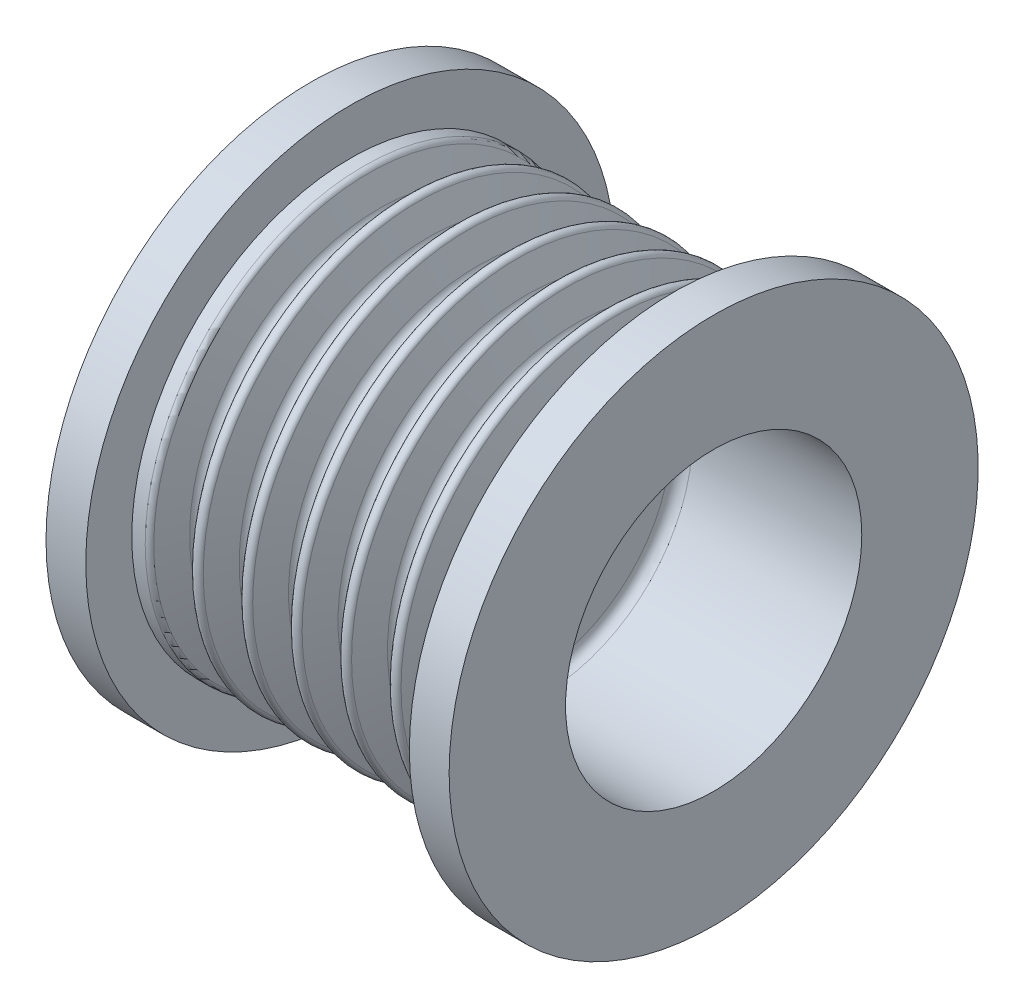
SolidWorks part; units mm, degrees
ref_plane "Front Plane" through (0, 0, 0) normal (0, 0, 1) x (1, 0, 0)
ref_plane "Top Plane" through (0, 0, 0) normal (0, 1, 0) x (1, 0, 0)
ref_plane "Right Plane" through (0, 0, 0) normal (1, 0, 0) x (0, 0, -1)
sketch "Sketch1" plane through (0, 0, 0) normal (0, 0, 1) x (1, 0, 0)
  line L4 (3, 12.5) -> (22.05, 12.5)
  line L5 (22.05, 12.5) -> (22.05, 4)
  line L10 (0, 0) -> (24, 0) construction
  line L12 (0, 4) -> (22.05, 4)
  line L13 (0, 4) -> (0, 8)
  line L14 (0, 8) -> (3, 8)
  line L15 (3, 8) -> (3, 12.5)
  dimension "D2" = 8
  dimension "D3" = 25
  dimension "D1" = 3
  dimension "D4" = 16
  dimension "D5" = 19.05
revolve "Revolve1" add sketch "Sketch1" angle 360 about L10
sketch "Sketch2" plane through (0, 0, 0) normal (0, 0, 1) x (1, 0, 0)
  line L0 (22.05, 0) -> (3, 0) construction
  line L1 (22.05, -12.5) -> (22.05, 12.5) construction
  line L3 (12.525, 0) -> (12.525, 12.5) construction
  line L4 (22.05, 12.5) -> (3, 12.5) construction
  line L5 (17.1986, 12.5) -> (19.5354, 12.5)
  line L6 (17.1986, 12.5) -> (17.1986, 10.3271)
  line L7 (19.5354, 12.5) -> (19.5354, 10.3271)
  line L8 (17.1986, 11.43) -> (19.5354, 11.43) construction
  line L9 (17.4373, 10.16) -> (17.8896, 8.9172)
  line L11 (18.8444, 8.9172) -> (19.2967, 10.16)
  line L12 (17.4373, 10.16) -> (19.2967, 10.16) construction
  line L13 (12.525, 12.5) -> (14.8618, 12.5) construction
  line L14 (14.8618, 12.5) -> (17.1986, 12.5) construction
  arc A0 (17.1986, 10.3271) -> (17.4373, 10.16) centre (17.1986, 10.0731) cw
  arc A1 (17.8896, 8.9172) -> (18.8444, 8.9172) centre (18.367, 9.0909) ccw
  arc A2 (19.5354, 10.3271) -> (19.2967, 10.16) centre (19.5354, 10.0731) ccw
  point P4 (0, 0)
  point P12 (0, 0)
  point P24 (9.525, -1.2265)
  point P25 (9.525, 0.8358)
  point P26 (0, 0)
  point P28 (9.525, 0)
  dimension "D3" = 0.254
  dimension "D6" = 0.508
  dimension "D1" = 2.3368
  dimension "D2" = 11.43
  dimension "D4" = 40
  dimension "D5" = 1.27
revolve "tooth groove" cut sketch "Sketch2" angle 360 about L0
pattern_linear "LPattern1" count 6 spacing 2.3368 along (-1, 0, 0) of "tooth groove"
sketch "Sketch3" plane through (0, 0, 0) normal (0, 0, 1) x (1, 0, 0)
  line L0 (22.05, 12.5) -> (19.5354, 12.5) construction
  line L2 (19.5354, 10.3271) -> (20.1704, 10.3271)
  line L4 (19.5354, 10.3271) -> (19.5354, 12.5)
  line L5 (19.5354, 12.5) -> (20.1704, 12.5)
  line L6 (20.1704, 10.3271) -> (20.1704, 12.5)
  line L7 (18.367, 8.5829) -> (18.367, 11.0958) construction
  line L8 (12.525, 10.3271) -> (12.525, 13.0355) construction
  line L9 (4.8796, 10.3271) -> (4.8796, 12.5)
  line L10 (5.5146, 12.5) -> (4.8796, 12.5)
  line L11 (5.5146, 10.3271) -> (5.5146, 12.5)
  line L12 (5.5146, 10.3271) -> (4.8796, 10.3271)
  line L13 (0, 0) -> (19.4427, 0) construction
  line L16 (19.5354, 10.3271) -> (19.5354, -10.3271) construction
  line L17 (19.5354, 10.3271) -> (19.5354, -10.3271) construction
  arc A3 (12.7637, 10.16) -> (12.2863, 10.16) centre (12.525, 10.0731) ccw construction
  arc A4 (17.8896, 8.9172) -> (18.8444, 8.9172) centre (18.367, 9.0909) ccw construction
  point P8 (0, 0)
  dimension "D1" = 1.8034
revolve "Cut-Revolve2" cut sketch "Sketch3" angle 360 about L13
sketch "Sketch5" plane through (22.05, 0, 0) normal (1, 0, 0) x (0, 0, -1)
  line L1 (1.5875, 2.4125) -> (-1.5875, 2.4125)
  line L2 (1.5875, 2.4125) -> (1.5875, 5.5875)
  line L3 (1.5875, 5.5875) -> (-1.5875, 5.5875)
  line L4 (-1.5875, 2.4125) -> (-1.5875, 5.5875)
  line L5 (1.5875, 2.4125) -> (-1.5875, 5.5875) construction
  line L6 (1.5875, 5.5875) -> (-1.5875, 2.4125) construction
  circle A0 centre (0, 0) radius 4 construction
  point P0 (0, 4)
  point P7 (0.4349, 3.9763)
  dimension "D1" = 3.175
  dimension "D2" = 3.175
extrude "keyway cut" cut sketch "Sketch5" against normal up to surface (22.05 mm away) contours L3 L4 L1 L2 up to face at (0, 0, 4)
sketch "Sketch6" plane through (22.05, 0, 0) normal (1, 0, 0) x (0, 0, -1)
  circle A0 centre (0, 0) radius 7
  dimension "D1" = 14
extrude "Cut-Extrude2" cut sketch "Sketch6" against normal blind 8.5
fillet "Fillet2" radius 0.5 1 edges at (13.55, 0, -7)
fillet "Fillet1" radius 1 1 edges at (3, 0, 8)
equation "\"D1@Sketch2\"=0.092in"
equation "\"D2@Sketch2\"=0.9in/2"
equation "\"D3@Sketch2\"=0.01in"
equation "\"D6@Sketch2\"=0.02in"
equation "\"D5@Sketch2\"=0.05in"
equation "\"D3@LPattern1\"=0.092in"
equation "\"D4@LPattern1\"=0.092in"
equation "\"D1@Sketch3\"=0.071in"
equation "\"D1@Sketch5\"=0.125in"
equation "\"D2@Sketch5\"=0.125in"
equation "\"D5@Sketch1\"=0.75in"
